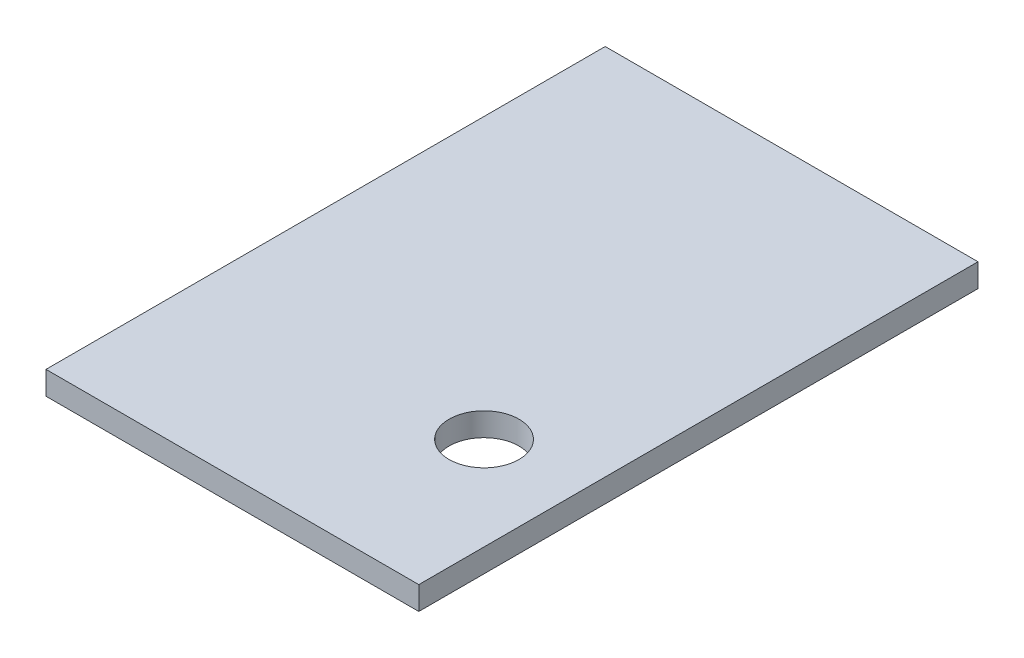
SolidWorks part; units mm, degrees
ref_plane "Front Plane" through (0, 0, 0) normal (0, 0, 1) x (1, 0, 0)
ref_plane "Top Plane" through (0, 0, 0) normal (0, 1, 0) x (1, 0, 0)
ref_plane "Right Plane" through (0, 0, 0) normal (1, 0, 0) x (0, 0, -1)
sketch "Sketch1" plane through (0, 0, 0) normal (0, 1, 0) x (1, 0, 0)
  line L1 (-25.4, 38.1) -> (25.4, 38.1)
  line L2 (-25.4, 38.1) -> (-25.4, -38.1)
  line L3 (-25.4, -38.1) -> (25.4, -38.1)
  line L4 (25.4, 38.1) -> (25.4, -38.1)
  line L5 (-25.4, 38.1) -> (25.4, -38.1) construction
  line L6 (-25.4, -38.1) -> (25.4, 38.1) construction
  point P4 (0, 0)
  dimension "D1" = 50.8
  dimension "D2" = 76.2
extrude "Boss-Extrude1" add sketch "Sketch1" along normal blind 3.175
sketch "Sketch2" plane through (0, 3.175, 0) normal (0, 1, 0) x (1, 0, 0)
  line L0 (12.7, 38.1) -> (12.7, -38.1) construction
  line L1 (25.4, 38.1) -> (-25.4, 38.1) construction
  line L2 (-25.4, -38.1) -> (25.4, -38.1) construction
  line L3 (-25.4, -16.51) -> (25.4, -16.51) construction
  line L4 (-25.4, 38.1) -> (-25.4, -38.1) construction
  line L5 (25.4, -38.1) -> (25.4, 38.1) construction
  circle A0 centre (12.7, -16.51) radius 4.7625
  point P14 (12.7, -12.3766)
  dimension "D3" = 9.525
  dimension "D1" = 38.1
  dimension "D2" = 54.61
extrude "Cut-Extrude1" cut sketch "Sketch2" against normal through all
